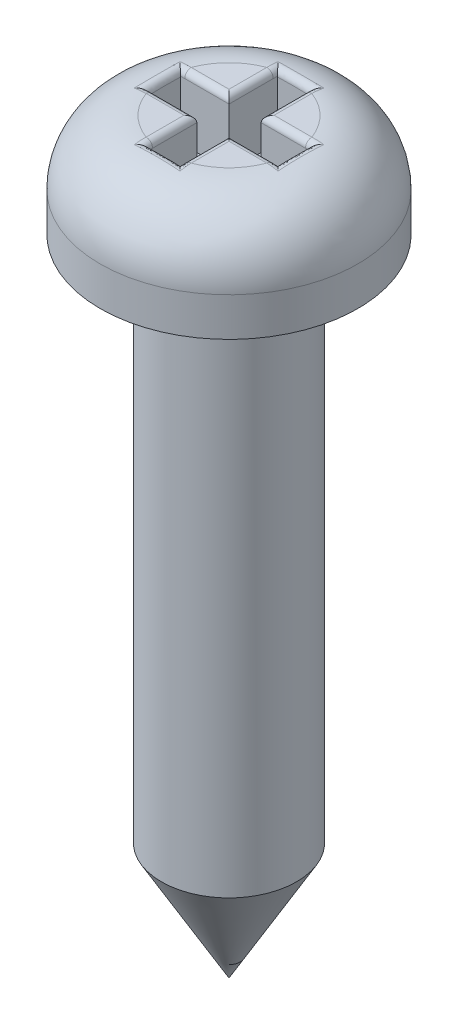
SolidWorks part; units mm, degrees
material "Stainless Steel (ferritic)"
ref_plane "Front Plane" through (0, 0, 0) normal (0, 0, 1) x (1, 0, 0)
ref_plane "Top Plane" through (0, 0, 0) normal (0, 1, 0) x (1, 0, 0)
ref_plane "Right Plane" through (0, 0, 0) normal (1, 0, 0) x (0, 0, -1)
sketch "Sketch1" plane through (0, 0, 0) normal (0, 1, 0) x (1, 0, 0)
  circle A0 centre (0, 0) radius 2
  dimension "D1" = 4
extrude "Boss-Extrude1" add sketch "Sketch1" along normal blind 0.6
sketch "Sketch3" plane through (0, 0.6, 0) normal (0, 1, 0) x (1, 0, 0)
  circle A0 centre (0, 0) radius 2
  dimension "D1" = 4
extrude "Boss-Extrude2" add sketch "Sketch3" along normal blind 1
fillet "Fillet1" radius 1 1 edges at (0, 1.6, 2)
sketch "Sketch4" plane through (0, 1.6, 0) normal (0, 1, 0) x (1, 0, 0)
  line L0 (-1, 0) -> (1, 0) construction
  line L1 (0, 1) -> (0, -1) construction
  line L2 (-1, -0.25) -> (-0.25, -0.25)
  line L3 (-0.25, 1) -> (-0.25, 0.25)
  line L4 (-1, 0.25) -> (-0.25, 0.25)
  line L5 (0.25, 1) -> (0.25, 0.25)
  line L6 (0.25, 1) -> (-0.25, 1)
  line L7 (0.25, -1) -> (-0.25, -1)
  line L8 (1, 0.25) -> (1, -0.25)
  line L9 (-1, 0.25) -> (-1, -0.25)
  line L10 (0.25, 0.25) -> (1, 0.25)
  line L11 (-1, 0.25) -> (1, 0.25) construction
  line L12 (0.25, -0.25) -> (0.25, -1)
  line L13 (0.25, 1) -> (0.25, -1) construction
  line L14 (0.25, -0.25) -> (1, -0.25)
  line L15 (-1, -0.25) -> (1, -0.25) construction
  line L16 (-0.25, -0.25) -> (-0.25, -1)
  line L17 (-0.25, 1) -> (-0.25, -1) construction
  point P4 (0, 0)
  point P10 (0, 0)
  dimension "D1" = 2
  dimension "D2" = 2
  dimension "D3" = 0.25
  dimension "D4" = 0.25
extrude "Cut-Extrude1" cut sketch "Sketch4" against normal blind 1
fillet "Fillet2" radius 0.1 20 edges at (0.25, 1.6, -0.6091) (-0.25, 1.6, 0.6091) (0.6091, 1.6, -0.25) (0.6091, 1.6, 0.25) (0.25, 1.6, 0.6091) (-0.6091, 1.6, 0.25) (-0.6091, 1.6, -0.25) (-0.25, 1.6, -0.6091)
sketch "Sketch5" plane through (0, 0, 0) normal (0, -1, 0) x (1, 0, 0)
  circle A0 centre (0, 0) radius 1.05
  dimension "D1" = 2.1
extrude "Boss-Extrude3" add sketch "Sketch5" along normal blind 10
chamfer "Chamfer1" distance 1.05 angle 60 1 edges at (0, -10, -1.05) first distance on face at (0, -10, -1.05)
